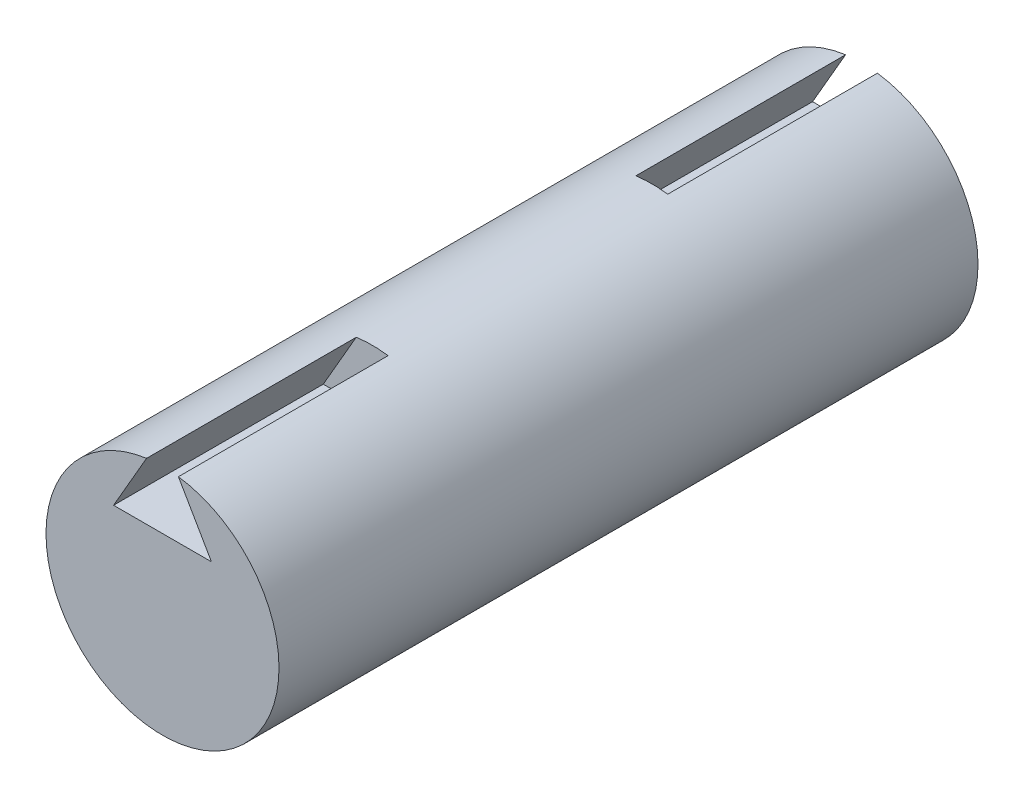
SolidWorks part; units mm, degrees
ref_plane "前视基准面" through (0, 0, 0) normal (0, 0, 1) x (1, 0, 0)
ref_plane "上视基准面" through (0, 0, 0) normal (0, 1, 0) x (1, 0, 0)
ref_plane "右视基准面" through (0, 0, 0) normal (1, 0, 0) x (0, 0, -1)
sketch "Sketch1" plane through (0, 0, 0) normal (0, 0, 1) x (1, 0, 0)
  line L0 (0, 0.0169) -> (0, 50000.0169) construction
  line L1 (-0.0684, 0.4953) -> (-0.21, 0.25)
  line L2 (-0.21, 0.25) -> (0.21, 0.25)
  line L3 (0.21, 0.25) -> (0.0684, 0.4953)
  arc A0 (-0.0684, 0.4953) -> (0.0684, 0.4953) centre (0, 0) ccw
  circle A1 centre (0, 0) radius 0.5
  point P11 (0, 0.25)
  dimension "D1" = 1
  dimension "D2" = 0.42
  dimension "D3" = 30
  dimension "D4" = 30
  dimension "D5" = 0.25
extrude "Boss-Extrude1" add sketch "Sketch1" along normal blind 3 contours A0 L0 L2 L1 | L0 A0 L3 L2 region at (0, -0.0338, 0)
extrude "Boss-Extrude2" add sketch "Sketch1<7>" along normal blind 1.2 from offset 0.9 contours A1
sketch "Sketch1<7>" plane through (0, 0, 0) normal (0, 0, 1) x (1, 0, 0) same geometry as "Sketch1"
